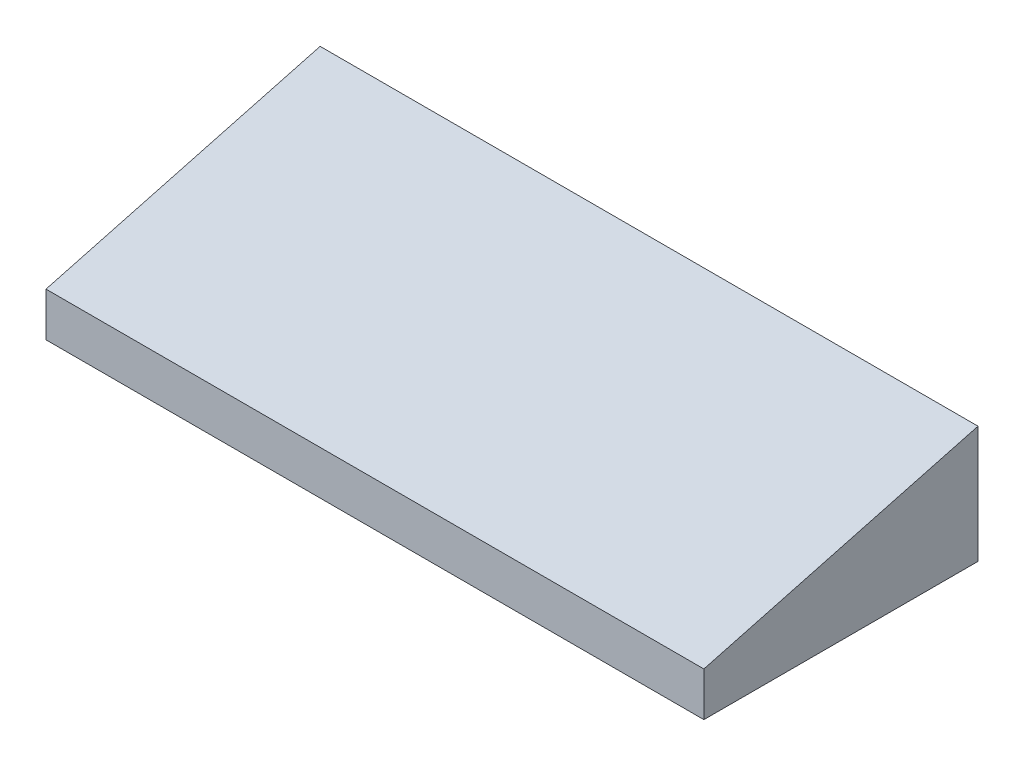
SolidWorks part; units mm, degrees
ref_plane "Front Plane" through (0, 0, 0) normal (0, 0, 1) x (1, 0, 0)
ref_plane "Top Plane" through (0, 0, 0) normal (0, 1, 0) x (1, 0, 0)
ref_plane "Right Plane" through (0, 0, 0) normal (1, 0, 0) x (0, 0, -1)
sketch "Sketch1" plane through (0, 0, 0) normal (1, 0, 0) x (0, 0, -1)
  line L0 (-40, 0) -> (40, 0)
  line L1 (-40, 0) -> (40, 21.3611)
  line L2 (40, 21.3611) -> (40, 0)
  line L3 (-10, 8.0104) -> (-10, 0)
  point P2 (0, 0)
  dimension "D1" = 80
  dimension "D2" = 14.95
  dimension "D3" = 21.3611
  dimension "D4" = 50
  dimension "D5" = 8.0104
extrude "Boss-Extrude1" add sketch "Sketch1" along normal blind 60 and the other way blind 60 contours L1 L3 L0 L2 region at (0, 7.8486, -18.7879)
